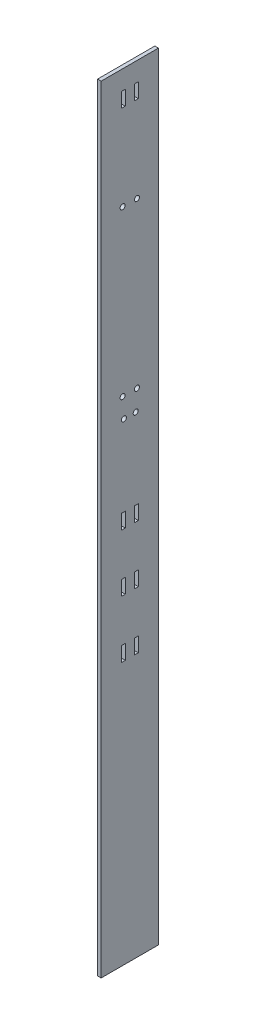
SolidWorks part; units mm, degrees
ref_plane "Front Plane" through (0, 0, 0) normal (0, 0, 1) x (1, 0, 0)
ref_plane "Top Plane" through (0, 0, 0) normal (0, 1, 0) x (1, 0, 0)
ref_plane "Right Plane" through (0, 0, 0) normal (1, 0, 0) x (0, 0, -1)
sketch "Sketch1" plane through (0, 0, 0) normal (1, 0, 0) x (0, 0, -1)
  line L1 (-25.4, 457.2) -> (25.4, 457.2)
  line L2 (-25.4, 457.2) -> (-25.4, -457.2)
  line L3 (-25.4, -457.2) -> (25.4, -457.2)
  line L4 (25.4, 457.2) -> (25.4, -457.2)
  line L5 (-25.4, 457.2) -> (25.4, -457.2) construction
  line L6 (-25.4, -457.2) -> (25.4, 457.2) construction
  point P0 (0, 0)
  dimension "D1" = 914.4
  dimension "D2" = 50.8
extrude "Boss-Extrude1" add sketch "Sketch1" along normal blind 3.175
sketch "Sketch2" plane through (3.175, 0, 0) normal (1, 0, 0) x (0, 0, -1)
  line L0 (-25.4, -457.2) -> (25.4, -457.2) construction
  line L1 (4, -204.5335) -> (7.556, -204.5335)
  line L2 (4, -204.5335) -> (4, -217.4875)
  line L3 (4, -217.4875) -> (7.556, -217.4875)
  line L4 (7.556, -204.5335) -> (7.556, -217.4875)
  line L5 (4, -204.5335) -> (7.556, -217.4875) construction
  line L6 (4, -217.4875) -> (7.556, -204.5335) construction
  point P0 (5.778, -211.0105)
  dimension "D1" = 3.556
  dimension "D2" = 12.954
  dimension "D3" = 239.7125
  dimension "D4" = 4
extrude "Cut-Extrude1" cut sketch "Sketch2" against normal through all
mirror "Mirror1" about plane through (0, 0, 0) normal (0, 0, 1) of "Cut-Extrude1"
pattern_linear "LPattern1" count 2 spacing 50.8 along (0, 1, 0) count 2 spacing 50.8 along (0, -1, 0) of "Mirror1"
sketch "Sketch3" plane through (3.175, 0, 0) normal (1, 0, 0) x (0, 0, -1)
  line L0 (7.556, -153.7335) -> (4, -153.7335) construction
  line L1 (4, 170.3705) -> (7.556, 170.3705)
  line L2 (4, 170.3705) -> (4, 157.4165)
  line L3 (4, 157.4165) -> (7.556, 157.4165)
  line L4 (7.556, 170.3705) -> (7.556, 157.4165)
  line L5 (4, 170.3705) -> (7.556, 157.4165) construction
  line L6 (4, 157.4165) -> (7.556, 170.3705) construction
  line L7 (7.556, -166.6875) -> (7.556, -153.7335) construction
  line L8 (4, -153.7335) -> (4, -166.6875) construction
  line L9 (0, 0) -> (0, 53.0447) construction
  line L10 (-4, 157.4165) -> (-7.556, 170.3705) construction
  line L11 (-4, 170.3705) -> (-7.556, 157.4165) construction
  line L12 (-7.556, 170.3705) -> (-7.556, 157.4165)
  line L13 (-4, 157.4165) -> (-7.556, 157.4165)
  line L14 (-4, 170.3705) -> (-4, 157.4165)
  line L15 (-4, 170.3705) -> (-7.556, 170.3705)
  point P0 (5.778, 163.8935)
  point P12 (5.778, 157.4165)
  point P19 (-5.778, 163.8935)
  dimension "D1" = 311.15
extrude "Cut-Extrude2" cut sketch "Sketch3" against normal through all
hole_wizard "#8 Clearance Hole1" positions "Sketch4" profile "Sketch5" hole size "#8" standard "ANSI Inch" end condition through all
sketch "Sketch4" plane through (3.175, 0, 0) normal (1, 0, 0) x (0, 0, -1)
  point P0 (6.35, -64.5237)
  point P3 (-6.35, -64.5237)
  point P6 (6.35, 81.272)
  point P9 (-6.35, 81.272)
  point P12 (5.25, -82.2261)
  point P15 (-5.25, -82.2261)
sketch "Sketch5" plane through (3.175, -64.5237, -6.35) normal (0, 1, 0) x (0, 0, -1)
  line L0 (0, 0) -> (0, 3.175)
  line L1 (0, 3.175) -> (2.2479, 3.175)
  line L2 (2.2479, 3.175) -> (2.2479, 0)
  line L5 (2.2479, 0) -> (0, 0)
  line L11 (0, -6.35) -> (0, 107.95) construction
  dimension "Thru Hole Dia." = 4.4958
  dimension "Thru Hole Depth" = 3.175
sketch "Sketch6" plane through (3.175, 0, 0) normal (1, 0, 0) x (0, 0, -1)
  line L0 (0, -457.2) -> (0, 187.325) construction
  line L1 (-25.4, -457.2) -> (25.4, -457.2) construction
  line L2 (-25.4, 187.325) -> (25.4, 187.325)
  line L4 (-25.4, 457.2) -> (-25.4, -457.2) construction
  line L5 (25.4, -457.2) -> (25.4, 457.2) construction
  point P9 (0, 0)
  dimension "D1" = 644.525
extrude "Cut-Extrude3" cut sketch "Sketch6" against normal through all and the other way through all
sketch "Sketch7" plane through (3.175, 0, 0) normal (1, 0, 0) x (0, 0, -1)
  line L0 (0, -457.2) -> (0, -501.65) construction
  line L1 (-25.4, -457.2) -> (25.4, -457.2) construction
  line L2 (-25.4, -457.2) -> (-25.4, -501.65)
  line L3 (-25.4, -501.65) -> (0, -501.65)
  line L4 (25.4, -457.2) -> (25.4, -501.65)
  line L5 (25.4, -501.65) -> (0, -501.65)
  line L6 (-25.4, -457.2) -> (25.4, -457.2)
  dimension "D1" = 44.45
extrude "Boss-Extrude2" add sketch "Sketch7" against normal up to surface (3.175 mm away) up to face at (0, -160.2105, 5.778)
